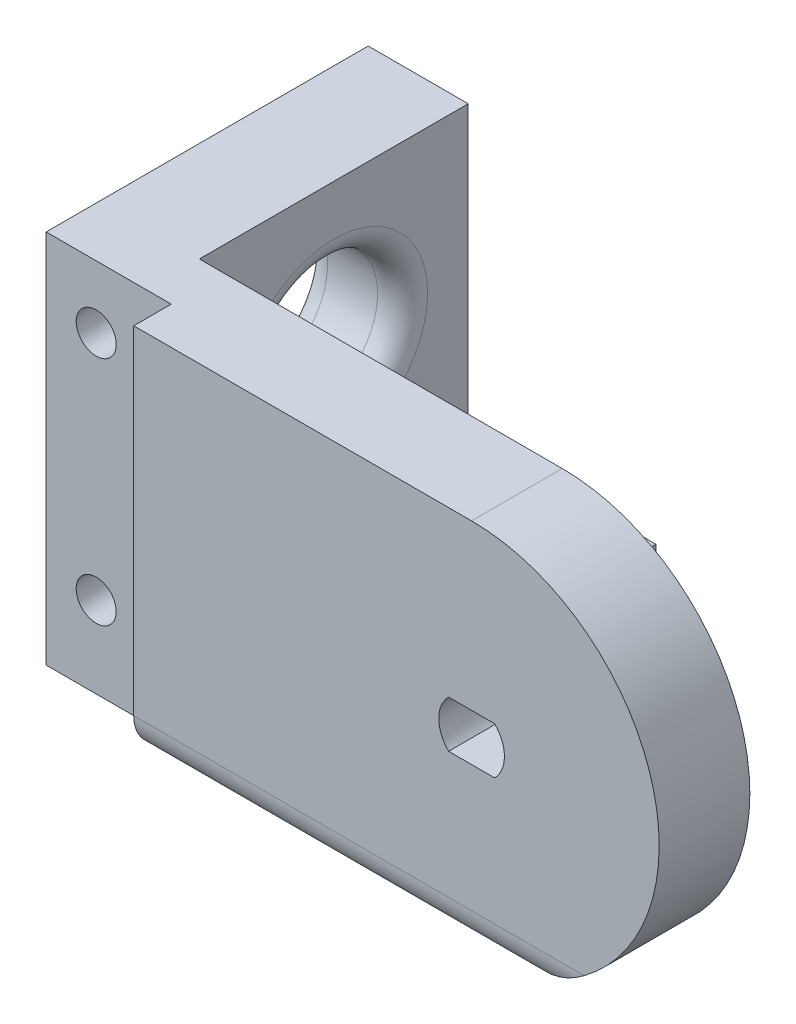
SolidWorks part; units mm, degrees
ref_plane "Front Plane" through (0, 0, 0) normal (0, 0, 1) x (1, 0, 0)
ref_plane "Top Plane" through (0, 0, 0) normal (0, 1, 0) x (1, 0, 0)
ref_plane "Right Plane" through (0, 0, 0) normal (1, 0, 0) x (0, 0, -1)
sketch "Sketch2" plane through (0, 0, -8) normal (0, 0, 1) x (1, 0, 0)
  line L0 (-25.7692, 245.1803) -> (-54.7874, 245.1803)
  line L1 (-54.7874, 245.1803) -> (-54.7874, 215.1803)
  line L2 (-54.7874, 215.1803) -> (-25.7692, 215.1803)
  arc A2 (-25.7692, 215.1803) -> (-25.7692, 245.1803) centre (-25.7692, 230.1803) ccw
  dimension "D1" = 29.0182
extrude "Boss-Extrude1" add sketch "Sketch2" along normal blind 8
sketch "Sketch3" plane through (0, 0, -28) normal (0, 0, -1) x (-1, 0, 0)
  line L3 (25.7692, 215.1803) -> (54.7874, 215.1803)
  line L4 (54.7874, 215.1803) -> (54.7874, 245.1803)
  line L5 (54.7874, 245.1803) -> (25.7692, 245.1803)
  line L6 (25.7692, 215.1803) -> (54.7874, 215.1803)
  line L7 (54.7874, 215.1803) -> (54.7874, 245.1803)
  line L8 (54.7874, 245.1803) -> (25.7692, 245.1803)
  arc A1 (25.7692, 245.1803) -> (25.7692, 215.1803) centre (25.7692, 230.1803) ccw
  arc A2 (25.7692, 245.1803) -> (25.7692, 215.1803) centre (25.7692, 230.1803) ccw
  dimension "D1" = 0
extrude "Boss-Extrude2" add sketch "Sketch3" along normal blind 8 separate body
sketch "Sketch4" plane through (-54.7874, 0, 0) normal (-1, 0, 0) x (0, 0, 1)
  line L1 (-36, 245.1803) -> (0, 245.1803)
  line L2 (-36, 245.1803) -> (-36, 215.1803)
  line L3 (-36, 215.1803) -> (0, 215.1803)
  line L4 (0, 245.1803) -> (0, 215.1803)
extrude "Boss-Extrude3" add sketch "Sketch4" along normal blind 8
sketch "Sketch6" plane through (0, 0, -36) normal (0, 0, -1) x (-1, 0, 0)
  line L0 (23.9321, 232.0553) -> (27.6063, 232.0553)
  line L1 (23.9321, 228.3053) -> (27.6063, 228.3053)
  arc A0 (23.9321, 232.0553) -> (23.9321, 228.3053) centre (25.7692, 230.1803) ccw
  arc A1 (27.6063, 228.3053) -> (27.6063, 232.0553) centre (25.7692, 230.1803) ccw
  dimension "D1" = 1.875
  dimension "D2" = 3.75
extrude "Cut-Extrude1" cut sketch "Sketch6" against normal up to surface (36 mm away) up to face at (-40.5283, 230.1803, 0)
sketch "Sketch7" plane through (-62.7874, 0, 0) normal (-1, 0, 0) x (0, 0, 1)
  line L0 (0, 215.1803) -> (0, 218.1803)
  line L1 (0, 215.1803) -> (0, 245.1803) construction
  line L2 (0, 215.1803) -> (-3, 215.1803)
  line L3 (-36, 215.1803) -> (0, 215.1803) construction
  line L4 (-18, 215.1803) -> (-18, 245.1803) construction
  line L5 (0, 245.1803) -> (-36, 245.1803) construction
  line L6 (-36, 215.1803) -> (-33, 215.1803)
  line L7 (-36, 215.1803) -> (-36, 218.1803)
  arc A0 (0, 218.1803) -> (-3, 215.1803) centre (-3, 218.1803) cw
  arc A1 (-36, 218.1803) -> (-33, 215.1803) centre (-33, 218.1803) ccw
extrude "Cut-Extrude2" cut sketch "Sketch7" against normal through all
sketch "Sketch8" plane through (0, 215.1803, 0) normal (0, -1, 0) x (1, 0, 0)
  line L0 (-54.7874, -8) -> (-25.7692, -8) construction
  line L1 (-56.7874, -28) -> (-39.7874, -28)
  line L2 (-56.7874, -28) -> (-56.7874, -8)
  line L3 (-56.7874, -8) -> (-39.7874, -8)
  line L4 (-39.7874, -28) -> (-39.7874, -8)
extrude "Boss-Extrude5" add sketch "Sketch8" against normal blind 7
sketch "Sketch10" plane through (0, 0, -28) normal (0, 0, 1) x (1, 0, 0)
  line L5 (-54.7874, 222.1803) -> (-39.7874, 222.1803)
  line L6 (-39.7874, 222.1803) -> (-39.7874, 215.1803)
  line L7 (-39.7874, 215.1803) -> (-25.7692, 215.1803)
  line L8 (-25.7692, 245.1803) -> (-54.7874, 245.1803)
  line L9 (-54.7874, 245.1803) -> (-54.7874, 222.1803)
  line L10 (-54.7874, 222.1803) -> (-39.7874, 222.1803)
  line L11 (-39.7874, 222.1803) -> (-39.7874, 215.1803)
  line L12 (-39.7874, 215.1803) -> (-25.7692, 215.1803)
  line L13 (-25.7692, 245.1803) -> (-54.7874, 245.1803)
  line L14 (-54.7874, 245.1803) -> (-54.7874, 222.1803)
  arc A1 (-25.7692, 215.1803) -> (-25.7692, 245.1803) centre (-25.7692, 230.1803) ccw
  arc A2 (-25.7692, 215.1803) -> (-25.7692, 245.1803) centre (-25.7692, 230.1803) ccw
  dimension "D1" = 0
extrude "Cut-Extrude3" cut sketch "Sketch10" against normal blind 0.75
sketch "Sketch11" plane through (0, 0, -8) normal (0, 0, -1) x (-1, 0, 0)
  line L5 (25.7692, 215.1803) -> (39.7874, 215.1803)
  line L6 (39.7874, 215.1803) -> (39.7874, 222.1803)
  line L7 (39.7874, 222.1803) -> (54.7874, 222.1803)
  line L8 (54.7874, 222.1803) -> (54.7874, 245.1803)
  line L9 (54.7874, 245.1803) -> (25.7692, 245.1803)
  line L10 (25.7692, 215.1803) -> (39.7874, 215.1803)
  line L11 (39.7874, 215.1803) -> (39.7874, 222.1803)
  line L12 (39.7874, 222.1803) -> (54.7874, 222.1803)
  line L13 (54.7874, 222.1803) -> (54.7874, 245.1803)
  line L14 (54.7874, 245.1803) -> (25.7692, 245.1803)
  arc A1 (25.7692, 245.1803) -> (25.7692, 215.1803) centre (25.7692, 230.1803) ccw
  arc A2 (25.7692, 245.1803) -> (25.7692, 215.1803) centre (25.7692, 230.1803) ccw
  dimension "D1" = 0
extrude "Cut-Extrude4" cut sketch "Sketch11" against normal blind 0.75
sketch "Sketch13" plane through (0, 0, -36) normal (0, 0, -1) x (-1, 0, 0)
  line L1 (52.7874, 245.1803) -> (65.2203, 245.1803)
  line L2 (52.7874, 245.1803) -> (52.7874, 215.1803)
  line L3 (52.7874, 215.1803) -> (65.2203, 215.1803)
  line L4 (65.2203, 245.1803) -> (65.2203, 215.1803)
extrude "Cut-Extrude6" cut sketch "Sketch13" against normal blind 3
sketch "Sketch14" plane through (0, 0, 0) normal (0, 0, 1) x (1, 0, 0)
  line L4 (-52.7874, 245.1803) -> (-62.7874, 245.1803)
  line L5 (-52.7874, 215.1803) -> (-52.7874, 245.1803)
  line L6 (-62.7874, 215.1803) -> (-52.7874, 215.1803)
  line L7 (-62.7874, 245.1803) -> (-62.7874, 215.1803)
  line L8 (-52.7874, 245.1803) -> (-62.7874, 245.1803)
  line L9 (-52.7874, 215.1803) -> (-52.7874, 245.1803)
  line L10 (-62.7874, 215.1803) -> (-52.7874, 215.1803)
  line L11 (-62.7874, 245.1803) -> (-62.7874, 215.1803)
  dimension "D1" = 0
extrude "Cut-Extrude7" cut sketch "Sketch14" against normal blind 3
sketch "Sketch15" plane through (0, 0, 0) normal (0, 0, 1) x (1, 0, 0)
  spline S0 degree 3 poles (-58.7873, 241.7803) (-61.9873, 241.7803) (-61.9873, 238.5803) (-58.7873, 238.5803) (-55.5873, 238.5803) (-55.5873, 241.7803) (-58.7873, 241.7803) (-61.9873, 241.7803) (-61.9873, 238.5803) knots -0.5 0 0 0 0.5 0.5 0.5 1 1 1 1.5 1.5 1.5 weights 1 0.333333 0.333333 1 0.333333 0.333333 1 0.333333 0.333333 only from (-58.7873, 241.7803) to (-58.7873, 241.7803) construction
  spline S1 degree 3 poles (-58.7873, 223.28) (-61.9873, 223.28) (-61.9873, 220.08) (-58.7873, 220.08) (-55.5873, 220.08) (-55.5873, 223.28) (-58.7873, 223.28) (-61.9873, 223.28) (-61.9873, 220.08) knots -0.5 0 0 0 0.5 0.5 0.5 1 1 1 1.5 1.5 1.5 weights 1 0.333333 0.333333 1 0.333333 0.333333 1 0.333333 0.333333 only from (-58.7873, 223.28) to (-58.7873, 223.28) construction
  spline S2 degree 3 poles (-58.7873, 241.7803) (-61.9873, 241.7803) (-61.9873, 238.5803) (-58.7873, 238.5803) (-55.5873, 238.5803) (-55.5873, 241.7803) (-58.7873, 241.7803) (-61.9873, 241.7803) (-61.9873, 238.5803) knots -0.5 0 0 0 0.5 0.5 0.5 1 1 1 1.5 1.5 1.5 weights 1 0.333333 0.333333 1 0.333333 0.333333 1 0.333333 0.333333 only from (-58.7873, 241.7803) to (-58.7873, 241.7803)
  spline S3 degree 3 poles (-58.7873, 223.28) (-61.9873, 223.28) (-61.9873, 220.08) (-58.7873, 220.08) (-55.5873, 220.08) (-55.5873, 223.28) (-58.7873, 223.28) (-61.9873, 223.28) (-61.9873, 220.08) knots -0.5 0 0 0 0.5 0.5 0.5 1 1 1 1.5 1.5 1.5 weights 1 0.333333 0.333333 1 0.333333 0.333333 1 0.333333 0.333333 only from (-58.7873, 223.28) to (-58.7873, 223.28)
extrude "Cut-Extrude8" cut sketch "Sketch15" against normal up to surface (36 mm away) up to face at (-25.7692, 230.1803, -36)
sketch "Sketch16" plane through (0, 0, -36) normal (0, 0, -1) x (-1, 0, 0)
  line L1 (75.759, 213.0722) -> (7.7191, 213.0722)
  line L2 (75.759, 213.0722) -> (75.759, 247.053)
  line L3 (75.759, 247.053) -> (7.7191, 247.053)
  line L4 (7.7191, 213.0722) -> (7.7191, 247.053)
extrude "Cut-Extrude9" cut sketch "Sketch16" against normal up to surface (7.25 mm away) up to face at (-37.6147, 227.5136, -28.75)
sketch "Sketch17" plane through (-54.7874, 0, 0) normal (1, 0, 0) x (0, 0, -1)
  line L0 (28.75, 233.6803) -> (7.25, 233.6803) construction
  line L1 (28.75, 245.1803) -> (28.75, 222.1803) construction
  line L2 (7.25, 215.1803) -> (7.25, 245.1803) construction
  circle A0 centre (18, 233.6803) radius 5.5
extrude "Cut-Extrude10" cut sketch "Sketch17" against normal up to surface (8 mm away) up to face at (-62.7874, 230.1803, -15.875)
fillet "Fillet1" radius 2 2 edges at (-62.7874, 233.6803, -12.5) (-54.7874, 233.6803, -23.5)
